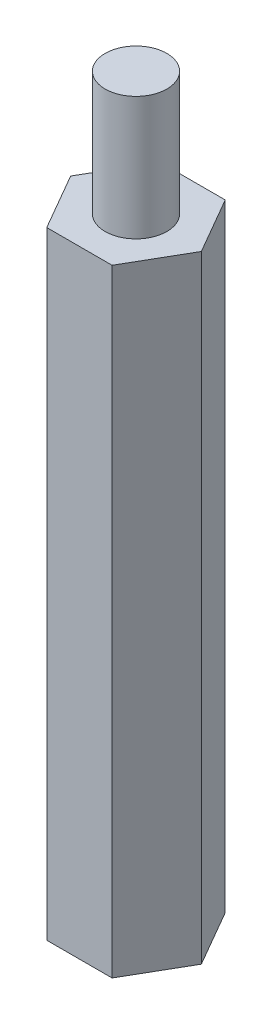
SolidWorks part; units mm, degrees
ref_plane "Front Plane" through (0, 0, 0) normal (0, 0, 1) x (1, 0, 0)
ref_plane "Top Plane" through (0, 0, 0) normal (0, 1, 0) x (1, 0, 0)
ref_plane "Right Plane" through (0, 0, 0) normal (1, 0, 0) x (0, 0, -1)
sketch "Sketch1" plane through (0, 0, 0) normal (0, 1, 0) x (1, 0, 0)
  line L1 (1.5877, -2.75) -> (3.1754, 0)
  line L2 (3.1754, 0) -> (1.5877, 2.75)
  line L3 (1.5877, 2.75) -> (-1.5877, 2.75)
  line L4 (-1.5877, 2.75) -> (-3.1754, 0)
  line L5 (-3.1754, 0) -> (-1.5877, -2.75)
  line L6 (-1.5877, -2.75) -> (1.5877, -2.75)
  circle A0 centre (0, 0) radius 2.75 construction
  dimension "D1" = 5.5
extrude "Boss-Extrude1" add sketch "Sketch1" along normal blind 30
sketch "Sketch2" plane through (0, 0, 0) normal (0, -1, 0) x (1, 0, 0)
  circle A0 centre (0, 0) radius 1.5
  dimension "D1" = 3
extrude "Cut-Extrude1" cut sketch "Sketch2" against normal blind 6
extrude "Boss-Extrude2" add sketch "Sketch2<2>" against normal blind 6 from surface starting at face at (0, 30, 0)
sketch "Sketch2<2>" plane through (0, 0, 0) normal (0, -1, 0) x (1, 0, 0) same geometry as "Sketch2"
